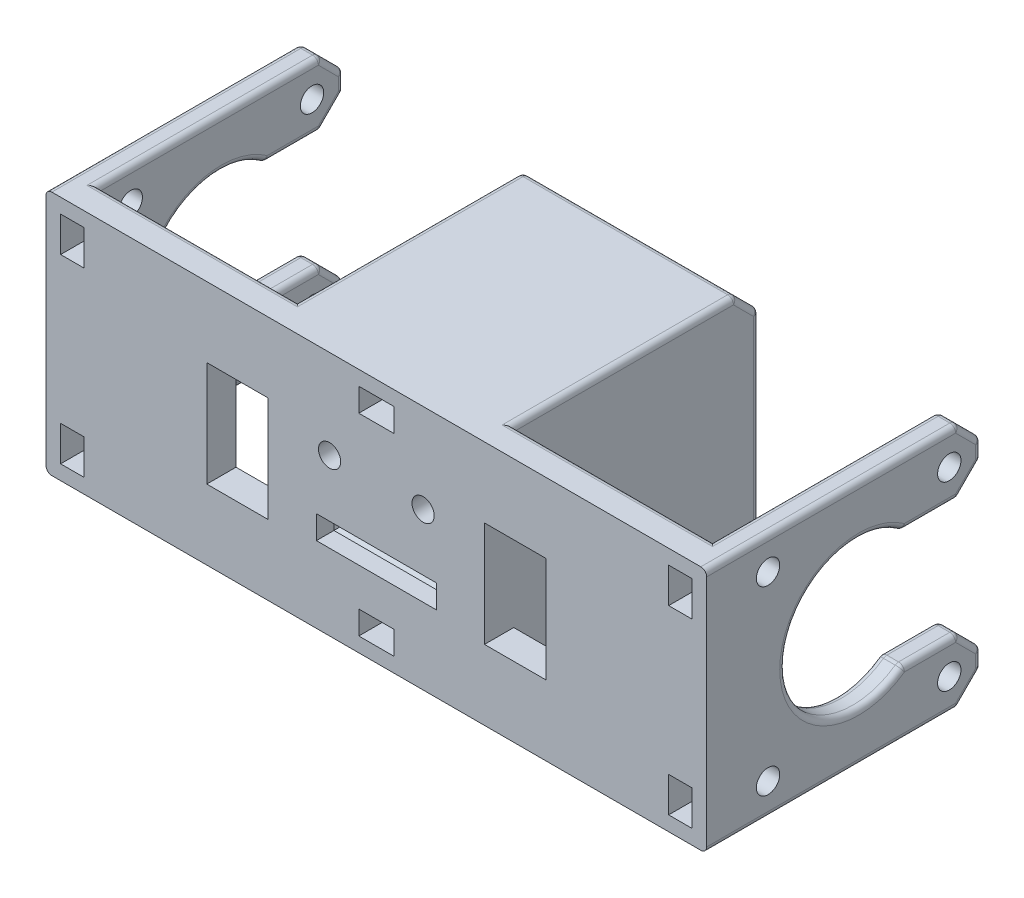
SolidWorks part; units mm, degrees
ref_plane "Plan de face" through (0, 0, 0) normal (0, 0, 1) x (1, 0, 0)
ref_plane "Plan de dessus" through (0, 0, 0) normal (0, 1, 0) x (1, 0, 0)
ref_plane "Plan de droite" through (0, 0, 0) normal (1, 0, 0) x (0, 0, -1)
sketch "Esquisse1" plane through (0, 0, 0) normal (0, 0, 1) x (1, 0, 0)
  line L1 (0, 0) -> (105, 0)
  line L2 (0, 0) -> (0, 42)
  line L3 (0, 42) -> (105, 42)
  line L4 (105, 0) -> (105, 42)
  line L5 (23.5, 30) -> (34, 30)
  line L6 (23.5, 30) -> (23.5, 12)
  line L7 (23.5, 12) -> (34, 12)
  line L8 (34, 30) -> (34, 12)
  line L9 (71, 30) -> (81.5, 30)
  line L10 (71, 30) -> (71, 12)
  line L11 (71, 12) -> (81.5, 12)
  line L12 (81.5, 30) -> (81.5, 12)
  point P13 (0, 21)
  dimension "D1" = 105
  dimension "D2" = 42
  dimension "D3" = 18
  dimension "D4" = 18
  dimension "D5" = 10.5
  dimension "D6" = 10.5
  dimension "D7" = 34
  dimension "D8" = 34
  dimension "D9" = 9
  dimension "D10" = 9
extrude "Boss.-Extru.1" add sketch "Esquisse1" along normal blind 5
sketch "Esquisse2" plane through (0, 0, 0) normal (0, 0, -1) x (-1, 0, 0)
  line L0 (-105, 42) -> (0, 42) construction
  line L1 (-71, 42) -> (-34, 42)
  line L2 (-71, 42) -> (-71, 0)
  line L3 (-71, 0) -> (-34, 0)
  line L4 (-34, 42) -> (-34, 0)
  line L5 (0, 0) -> (-105, 0) construction
  line L6 (-71, 30) -> (-71, 12) construction
  line L7 (-34, 12) -> (-34, 30) construction
  dimension "D1" = 0
  dimension "D2" = 0
extrude "Boss.-Extru.2" add sketch "Esquisse2" along normal blind 42
chamfer "Chanfrein1" distance 4 angle 45 2 edges at (52.5, 0, -42) (52.5, 42, -42)
sketch "Esquisse3" plane through (105, 0, 0) normal (1, 0, 0) x (0, 0, -1)
  line L1 (0, 0) -> (0, 42) construction
  line L2 (-5, 0) -> (-5, 42) construction
  line L3 (-5, 0) -> (42, 0)
  line L4 (42, 0) -> (42, 11)
  line L5 (42, 38) -> (42, 4) construction
  line L6 (42, 11) -> (28.5, 11)
  line L7 (28.5, 31) -> (42, 31)
  line L8 (42, 31) -> (42, 42)
  line L9 (42, 42) -> (-5, 42)
  line L10 (-5, 42) -> (-5, 0)
  line L12 (0, 12) -> (0, 0) construction
  arc A0 (28.5, 31) -> (28.5, 11) centre (21, 21) ccw
  circle A1 centre (36.5, 36.5) radius 2
  circle A2 centre (36.5, 5.5) radius 2
  circle A3 centre (5.5, 5.5) radius 2
  circle A4 centre (5.5, 36.5) radius 2
  point P9 (-5, 21)
  point P29 (2.1469, 36.6815)
  dimension "D1" = 12.5
  dimension "D4" = 11
  dimension "D5" = 4
  dimension "D10" = 4
  dimension "D15" = 4
  dimension "D16" = 4
  dimension "D2" = 21
  dimension "D3" = 0
  dimension "D6" = 5.5
  dimension "D7" = 5.5
  dimension "D8" = 5.5
  dimension "D9" = 5.5
  dimension "D11" = 5.5
  dimension "D12" = 5.5
  dimension "D13" = 5.5
  dimension "D14" = 5.5
extrude "Boss.-Extru.3" add sketch "Esquisse3" along normal blind 4
extrude "Boss.-Extru.4" add sketch "Esquisse3<2>" against normal blind 4 from surface starting at face at (0, 21, 2.5)
sketch "Esquisse3<2>" plane through (105, 0, 0) normal (1, 0, 0) x (0, 0, -1) same geometry as "Esquisse3"
chamfer "Chanfrein2" distance 4 angle 45 8 edges at (107, 11, -42) (107, 0, -42) (107, 31, -42) (107, 42, -42) (-2, 0, -42) (-2, 11, -42) (-2, 31, -42) (-2, 42, -42)
sketch "Esquisse4" plane through (0, 0, 5) normal (0, 0, 1) x (1, 0, 0)
  line L0 (42.25, 29) -> (62.75, 29) construction
  line L1 (62.75, 29) -> (62.75, 13) construction
  line L2 (62.75, 13) -> (42.25, 13) construction
  line L3 (42.25, 13) -> (42.25, 29) construction
  line L4 (34, 12) -> (34, 30) construction
  line L7 (109, 42) -> (-4, 42) construction
  circle A0 centre (44.5, 26.75) radius 1.9
  circle A1 centre (60.5, 26.75) radius 1.9
  dimension "D6" = 3.8
  dimension "D7" = 3.8
  dimension "D1" = 16
  dimension "D2" = 20.5
  dimension "D3" = 8.25
  dimension "D4" = 13
  dimension "D5" = 16
  dimension "D8" = 2.25
  dimension "D9" = 2.25
extrude "Enlèv. mat.-Extru.1" cut sketch "Esquisse4" against normal blind 12
sketch "Esquisse5" plane through (0, 0, 5) normal (0, 0, 1) x (1, 0, 0)
  line L0 (42.25, 29) -> (62.75, 29) construction
  line L1 (42.25, 17) -> (62.75, 17)
  line L2 (42.25, 17) -> (42.25, 13)
  line L3 (42.25, 13) -> (62.75, 13)
  line L4 (62.75, 17) -> (62.75, 13)
  line L5 (62.75, 29) -> (62.75, 13) construction
  line L6 (62.75, 13) -> (42.25, 13) construction
  line L7 (42.25, 13) -> (42.25, 29) construction
  circle A0 centre (44.5, 26.75) radius 1.9 construction
  circle A1 centre (44.5, 26.75) radius 1.9 construction
  point P1 (0, 0)
  point P2 (42.25, 14.9085)
  point P6 (42.3005, 29.0746)
  point P10 (41.8149, 30.5316)
  point P14 (0, 0)
  point P15 (0, 0)
  point P16 (41.8879, 13)
  point P17 (63.0968, 13)
  dimension "D3" = 2.25
  dimension "D4" = 2.25
  dimension "D1" = 16
  dimension "D2" = 20.5
  dimension "D5" = 4
extrude "Enlèv. mat.-Extru.2" cut sketch "Esquisse5" against normal blind 4
sketch "Esquisse6" plane through (0, 0, 5) normal (0, 0, 1) x (1, 0, 0)
  line L0 (109, 42) -> (-4, 42) construction
  line L1 (-1.5, 2.5) -> (2.5, 2.5)
  line L2 (-1.5, 2.5) -> (-1.5, 8.5)
  line L3 (-1.5, 8.5) -> (2.5, 8.5)
  line L4 (2.5, 2.5) -> (2.5, 8.5)
  line L5 (-1.5, 39.5) -> (2.5, 39.5)
  line L6 (-1.5, 39.5) -> (-1.5, 33.5)
  line L7 (-1.5, 33.5) -> (2.5, 33.5)
  line L8 (2.5, 39.5) -> (2.5, 33.5)
  line L9 (-4, 42) -> (-4, 0) construction
  line L10 (-4, 0) -> (109, 0) construction
  dimension "D1" = 4
  dimension "D2" = 6
  dimension "D3" = 6
  dimension "D4" = 4
  dimension "D5" = 2.5
  dimension "D6" = 2.5
  dimension "D7" = 2.5
  dimension "D8" = 2.5
extrude "Enlèv. mat.-Extru.3" cut sketch "Esquisse6" against normal blind 5
sketch "Esquisse7" plane through (-4, 0, 0) normal (-1, 0, 0) x (0, 0, 1)
  line L0 (5, 39.5) -> (5, 33.5) construction
  line L1 (5, 8.5) -> (5, 2.5) construction
  line L2 (5, 42) -> (5, 0) construction
  circle A0 centre (2.5, 36.5) radius 1.375
  circle A1 centre (2.5, 5.5) radius 1.375
  point P6 (5, 36.5)
  point P9 (5, 5.5)
  dimension "D1" = 2.75
  dimension "D2" = 2.75
  dimension "D3" = 0
  dimension "D4" = 0
  dimension "D5" = 2.5
  dimension "D6" = 2.5
ref_plane "Plan1" through (52.5, 0, 0) normal (1, 0, 0) x (0, 0, -1)
sketch "Esquisse9" plane through (0, 0, 5) normal (0, 0, 1) x (1, 0, 0)
  line L0 (-4, 0) -> (109, 0) construction
  line L1 (49.5, 39.5) -> (55.5, 39.5)
  line L2 (49.5, 39.5) -> (49.5, 35.5)
  line L3 (49.5, 35.5) -> (55.5, 35.5)
  line L4 (55.5, 39.5) -> (55.5, 35.5)
  line L5 (49.5, 6.5) -> (55.5, 6.5)
  line L6 (49.5, 6.5) -> (49.5, 2.5)
  line L7 (49.5, 2.5) -> (55.5, 2.5)
  line L8 (55.5, 6.5) -> (55.5, 2.5)
  line L9 (52.5, -23.1) -> (52.5, 23.1) construction
  line L10 (109, 42) -> (-4, 42) construction
  point P10 (61.2424, 2.5)
  point P13 (52.5, 2.5)
  point P14 (52.5, 39.5)
  dimension "D1" = 6
  dimension "D2" = 6
  dimension "D3" = 4
  dimension "D4" = 4
  dimension "D5" = 2.5
  dimension "D6" = 0
  dimension "D7" = 0
  dimension "D8" = 2.5
extrude "Enlèv. mat.-Extru.6" cut sketch "Esquisse9" against normal blind 7
fillet "Congé1" radius 1 24 edges at (-2, 31, -28.5) (-2, 31, -38) (-2, 42, -38) (-2, 38, -42) (-2, 35, -42) (-2, 11, -28.5) (-2, 11, -38) (-2, 7, -42) (-2, 4, -42) (-2, 0, -38) (52.5, 38, -42) (52.5, 42, -38) (52.5, 4, -42) (52.5, 0, -38) (107, 0, -38) (107, 4, -42) (107, 7, -42) (107, 11, -28.5) (107, 11, -38) (107, 42, -38) (107, 38, -42) (107, 35, -42) (107, 31, -28.5) (107, 31, -38)
fillet "Congé2" radius 1 106 edges at (0, 0, -18.7929) (0, 0.0761, -37.9685) (0, 2, -40) (0, 4.0315, -41.9239) (0, 5.5, -42) (0, 6.9685, -41.9239) (0, 9, -40) (0, 10.9239, -37.9685) (0, 11, -33.206) (0, 10.9526, -28.5219) (0, 21, -8.5) (0, 31.0474, -28.5219) (0, 31, -33.206) (0, 31.0761, -37.9685) (0, 33, -40) (0, 35.0315, -41.9239) (0, 36.5, -42) (0, 37.9685, -41.9239) (0, 40, -40) (0, 41.9239, -37.9685) (109, 0, -16.2929) (109, 0.0761, -37.9685) (109, 2, -40) (109, 4.0315, -41.9239) (109, 5.5, -42) (109, 6.9685, -41.9239) (109, 9, -40) (109, 10.9239, -37.9685) (109, 11, -33.206) (109, 10.9526, -28.5219) (109, 21, -8.5) (109, 31.0474, -28.5219) (109, 31, -33.206) (109, 31.0761, -37.9685) (109, 33, -40) (109, 35.0315, -41.9239) (109, 36.5, -42) (109, 37.9685, -41.9239) (109, 40, -40) (109, 41.9239, -37.9685) (105, 0, -18.7929) (105, 0.0761, -37.9685) (105, 2, -40) (105, 4.0315, -41.9239) (105, 5.5, -42) (105, 6.9685, -41.9239) (105, 9, -40) (105, 10.9239, -37.9685) (105, 11, -33.206) (105, 10.9526, -28.5219) (105, 21, -8.5) (105, 31.0474, -28.5219) (105, 31, -33.206) (105, 31.0761, -37.9685) (105, 33, -40) (105, 35.0315, -41.9239) (105, 36.5, -42) (105, 37.9685, -41.9239) (105, 40, -40) (105, 41.9239, -37.9685) (71, 0, -18.7929) (71, 0.0761, -37.9685) (71, 2, -40) (71, 4.0315, -41.9239) (71, 21, -42) (71, 37.9685, -41.9239) (71, 40, -40) (71, 41.9239, -37.9685) (34, 0, -18.7929) (34, 0.0761, -37.9685) (34, 2, -40) (34, 4.0315, -41.9239) (34, 21, -42) (34, 37.9685, -41.9239) (34, 40, -40) (34, 41.9239, -37.9685) (-4, 0, -16.2929) (-4, 0.0761, -37.9685) (-4, 2, -40) (-4, 4.0315, -41.9239) (-4, 5.5, -42) (-4, 6.9685, -41.9239) (-4, 9, -40) (-4, 10.9239, -37.9685) (-4, 11, -33.206) (-4, 10.9526, -28.5219) (-4, 21, -8.5) (-4, 31.0474, -28.5219) (-4, 31, -33.206) (-4, 31.0761, -37.9685) (-4, 33, -40) (-4, 35.0315, -41.9239) (-4, 36.5, -42) (-4, 37.9685, -41.9239) (-4, 40, -40) (-4, 41.9239, -37.9685) (88, 0, 0) (17, 0, 0) (17, 42, 0) (88, 42, 0) (0, 42, -18.7929) (109, 42, -16.2929) (105, 42, -18.7929) (71, 42, -18.7929) (34, 42, -18.7929) (-4, 42, -16.2929)
chamfer "Chanfrein3" distance 1.5 angle 45 2 edges at (46.4, 26.75, -7) (62.4, 26.75, -7)
chamfer "Chanfrein4" distance 1 angle 45 4 edges at (52.5, 17, 1) (62.75, 15, 1) (52.5, 13, 1) (42.25, 15, 1)
chamfer "Chanfrein5" distance 1.5 angle 45 8 edges at (52.5, 39.5, -2) (55.5, 37.5, -2) (52.5, 35.5, -2) (49.5, 37.5, -2) (52.5, 6.5, -2) (55.5, 4.5, -2) (52.5, 2.5, -2) (49.5, 4.5, -2)
mirror "Symétrie2" about plane through (52.5, 0, 0) normal (1, 0, 0) of "Enlèv. mat.-Extru.3"
chamfer "Chanfrein6" distance 1.5 angle 45 4 edges at (0, 36.5, 0) (0, 5.5, 0) (105, 5.5, 0) (105, 36.5, 0)
